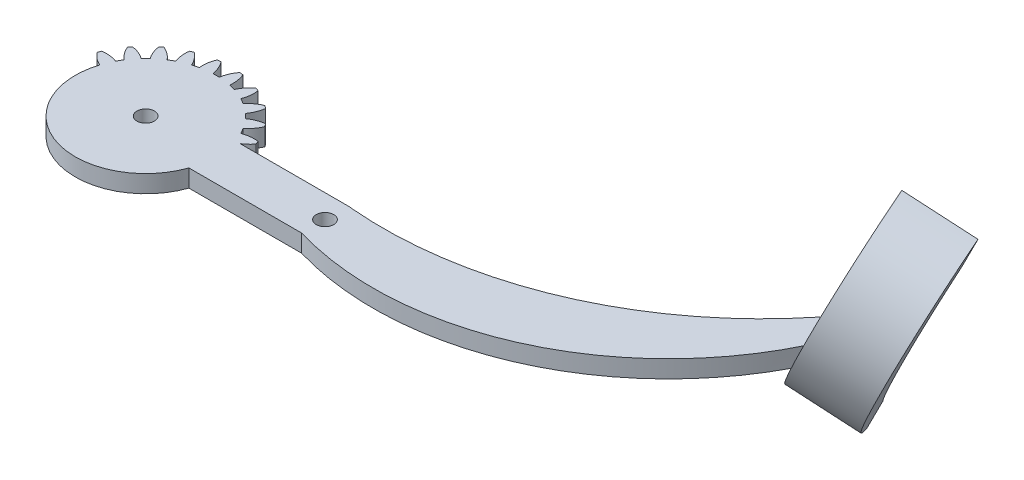
SolidWorks part; units mm, degrees
ref_plane "Front Plane" through (0, 0, 0) normal (0, 0, 1) x (1, 0, 0)
ref_plane "Top Plane" through (0, 0, 0) normal (0, 1, 0) x (1, 0, 0)
ref_plane "Right Plane" through (0, 0, 0) normal (1, 0, 0) x (0, 0, -1)
sketch "Sketch1" plane through (0, 0, 0) normal (0, 1, 0) x (1, 0, 0)
  line L0 (20.6437, 4) -> (2.0816, 4)
  line L1 (2.0816, -4) -> (20.6437, -4)
  arc A0 (2.0816, 4) -> (3.5217, 5.3071) centre (-0.7683, 8.5867) ccw
  arc A1 (3.5217, 5.3071) -> (3.2829, 5.8838) centre (-10.1063, 0) ccw
  arc A2 (3.2829, 5.8838) -> (0.6271, 5.5703) centre (2.5684, 0.5313) ccw
  arc A3 (0.6271, 5.5703) -> (0.0844, 6.5103) centre (-10.1063, 0) ccw
  arc A4 (0.0844, 6.5103) -> (1.6838, 8.6535) centre (-3.3089, 10.711) ccw
  arc A5 (1.6838, 8.6535) -> (1.3038, 9.1487) centre (-10.1063, 0) ccw
  arc A6 (1.3038, 9.1487) -> (-1.1803, 8.1585) centre (1.999, 3.7936) ccw
  arc A7 (-1.1803, 8.1585) -> (-1.9479, 8.926) centre (-10.1063, 0) ccw
  arc A8 (-1.9479, 8.926) -> (-0.9576, 11.4102) centre (-6.3127, 12.1053) ccw
  arc A9 (-0.9576, 11.4102) -> (-1.4528, 11.7901) centre (-10.1063, 0) ccw
  arc A10 (-1.4528, 11.7901) -> (-3.596, 10.1907) centre (0.6046, 6.7975) ccw
  arc A11 (-3.596, 10.1907) -> (-4.5361, 10.7334) centre (-10.1063, 0) ccw
  arc A12 (-4.5361, 10.7334) -> (-4.2225, 13.3892) centre (-9.5751, 12.6747) ccw
  arc A13 (-4.2225, 13.3892) -> (-4.7992, 13.6281) centre (-10.1063, 0) ccw
  arc A14 (-4.7992, 13.6281) -> (-6.4554, 11.5285) centre (-1.5196, 9.3381) ccw
  arc A15 (-6.4554, 11.5285) -> (-7.5039, 11.8094) centre (-10.1063, 0) ccw
  arc A16 (-7.5039, 11.8094) -> (-7.8884, 14.4558) centre (-12.8736, 12.3803) ccw
  arc A17 (-7.8884, 14.4558) -> (-8.5072, 14.5373) centre (-10.1063, 0) ccw
  arc A18 (-8.5072, 14.5373) -> (-9.5636, 12.0806) centre (-4.2291, 11.2423) ccw
  arc A19 (-9.5636, 12.0806) -> (-10.6491, 12.0806) centre (-10.1063, 0) ccw
  arc A20 (-10.6491, 12.0806) -> (-11.7054, 14.5373) centre (-15.9836, 11.2423) ccw
  arc A21 (-11.7054, 14.5373) -> (-12.3243, 14.4558) centre (-10.1063, 0) ccw
  arc A22 (-12.3243, 14.4558) -> (-12.7088, 11.8094) centre (-7.3391, 12.3803) ccw
  arc A23 (-12.7088, 11.8094) -> (-13.7573, 11.5285) centre (-10.1063, 0) ccw
  arc A24 (-13.7573, 11.5285) -> (-15.4135, 13.6281) centre (-18.6931, 9.3381) ccw
  arc A25 (-15.4135, 13.6281) -> (-15.9901, 13.3892) centre (-10.1063, 0) ccw
  arc A26 (-15.9901, 13.3892) -> (-15.6766, 10.7334) centre (-10.6376, 12.6747) ccw
  arc A27 (-15.6766, 10.7334) -> (-16.6166, 10.1907) centre (-10.1063, 0) ccw
  arc A28 (-16.6166, 10.1907) -> (-18.7599, 11.7901) centre (-20.8173, 6.7975) ccw
  arc A29 (-18.7599, 11.7901) -> (-19.255, 11.4102) centre (-10.1063, 0) ccw
  arc A30 (-19.255, 11.4102) -> (-18.2648, 8.926) centre (-13.9, 12.1053) ccw
  arc A31 (-18.2648, 8.926) -> (-19.0324, 8.1585) centre (-10.1063, 0) ccw
  arc A32 (-19.0324, 8.1585) -> (-21.5165, 9.1487) centre (-22.2117, 3.7936) ccw
  arc A33 (-21.5165, 9.1487) -> (-21.8965, 8.6535) centre (-10.1063, 0) ccw
  arc A34 (-21.8965, 8.6535) -> (-20.2971, 6.5103) centre (-16.9038, 10.711) ccw
  arc A35 (-20.2971, 6.5103) -> (-20.8398, 5.5703) centre (-10.1063, 0) ccw
  arc A36 (-20.8398, 5.5703) -> (-23.4956, 5.8838) centre (-22.7811, 0.5313) ccw
  arc A37 (-23.4956, 5.8838) -> (-23.7344, 5.3071) centre (-10.1063, 0) ccw
  arc A38 (-23.7344, 5.3071) -> (-21.6348, 3.6509) centre (-19.4444, 8.5867) ccw
  arc A39 (-21.6348, 3.6509) -> (-21.9157, 2.6025) centre (-10.1063, 0) ccw
  arc A40 (-21.9157, 2.6025) -> (-24.5622, 2.2179) centre (-22.4867, -2.7673) ccw
  arc A41 (-24.5622, 2.2179) -> (-24.6437, 1.5991) centre (-10.1063, 0) ccw
  arc A42 (-24.6437, 1.5991) -> (-22.1869, 0.5427) centre (-21.3486, 5.8773) ccw
  arc A43 (-22.1869, 0.5427) -> (-22.1869, -0.5427) centre (-10.1063, 0) ccw
  arc A44 (-22.1869, -0.5427) -> (-24.6437, -1.5991) centre (-21.3486, -5.8773) ccw
  arc A45 (-24.6437, -1.5991) -> (-24.5622, -2.2179) centre (-10.1063, 0) ccw
  arc A46 (-24.5622, -2.2179) -> (-21.9157, -2.6025) centre (-22.4867, 2.7673) ccw
  arc A47 (-21.9157, -2.6025) -> (-21.6348, -3.6509) centre (-10.1063, 0) ccw
  arc A48 (-21.6348, -3.6509) -> (-23.7344, -5.3071) centre (-19.4444, -8.5867) ccw
  arc A49 (-23.7344, -5.3071) -> (-23.4956, -5.8838) centre (-10.1063, 0) ccw
  arc A50 (-23.4956, -5.8838) -> (-20.8398, -5.5703) centre (-22.7811, -0.5313) ccw
  arc A51 (-20.8398, -5.5703) -> (-20.2971, -6.5103) centre (-10.1063, 0) ccw
  arc A52 (-20.2971, -6.5103) -> (-21.8965, -8.6535) centre (-16.9038, -10.711) ccw
  arc A53 (-21.8965, -8.6535) -> (-21.5165, -9.1487) centre (-10.1063, 0) ccw
  arc A54 (-21.5165, -9.1487) -> (-19.0324, -8.1585) centre (-22.2117, -3.7936) ccw
  arc A55 (-19.0324, -8.1585) -> (-18.2648, -8.926) centre (-10.1063, 0) ccw
  arc A56 (-18.2648, -8.926) -> (-19.255, -11.4102) centre (-13.9, -12.1053) ccw
  arc A57 (-19.255, -11.4102) -> (-18.7599, -11.7901) centre (-10.1063, 0) ccw
  arc A58 (-18.7599, -11.7901) -> (-16.6166, -10.1907) centre (-20.8173, -6.7975) ccw
  arc A59 (-16.6166, -10.1907) -> (-15.6766, -10.7334) centre (-10.1063, 0) ccw
  arc A60 (-15.6766, -10.7334) -> (-15.9901, -13.3892) centre (-10.6376, -12.6747) ccw
  arc A61 (-15.9901, -13.3892) -> (-15.4135, -13.6281) centre (-10.1063, 0) ccw
  arc A62 (-15.4135, -13.6281) -> (-13.7573, -11.5285) centre (-18.6931, -9.3381) ccw
  arc A63 (-13.7573, -11.5285) -> (-12.7088, -11.8094) centre (-10.1063, 0) ccw
  arc A64 (-12.7088, -11.8094) -> (-12.3243, -14.4558) centre (-7.3391, -12.3803) ccw
  arc A65 (-12.3243, -14.4558) -> (-11.7054, -14.5373) centre (-10.1063, 0) ccw
  arc A66 (-11.7054, -14.5373) -> (-10.6491, -12.0806) centre (-15.9836, -11.2423) ccw
  arc A67 (-10.6491, -12.0806) -> (-9.5636, -12.0806) centre (-10.1063, 0) ccw
  arc A68 (-9.5636, -12.0806) -> (-8.5072, -14.5373) centre (-4.2291, -11.2423) ccw
  arc A69 (-8.5072, -14.5373) -> (-7.8884, -14.4558) centre (-10.1063, 0) ccw
  arc A70 (-7.8884, -14.4558) -> (-7.5039, -11.8094) centre (-12.8736, -12.3803) ccw
  arc A71 (-7.5039, -11.8094) -> (-6.4554, -11.5285) centre (-10.1063, 0) ccw
  arc A72 (-6.4554, -11.5285) -> (-4.7992, -13.6281) centre (-1.5196, -9.3381) ccw
  arc A73 (-4.7992, -13.6281) -> (-4.2225, -13.3892) centre (-10.1063, 0) ccw
  arc A74 (-4.2225, -13.3892) -> (-4.5361, -10.7334) centre (-9.5751, -12.6747) ccw
  arc A75 (-4.5361, -10.7334) -> (-3.596, -10.1907) centre (-10.1063, 0) ccw
  arc A76 (-3.596, -10.1907) -> (-1.4528, -11.7901) centre (0.6046, -6.7975) ccw
  arc A77 (-1.4528, -11.7901) -> (-0.9576, -11.4102) centre (-10.1063, 0) ccw
  arc A78 (-0.9576, -11.4102) -> (-1.9479, -8.926) centre (-6.3127, -12.1053) ccw
  arc A79 (-1.9479, -8.926) -> (-1.1803, -8.1585) centre (-10.1063, 0) ccw
  arc A80 (-1.1803, -8.1585) -> (1.3038, -9.1487) centre (1.999, -3.7936) ccw
  arc A81 (1.3038, -9.1487) -> (1.6838, -8.6535) centre (-10.1063, 0) ccw
  arc A82 (1.6838, -8.6535) -> (0.0844, -6.5103) centre (-3.3089, -10.711) ccw
  arc A83 (0.0844, -6.5103) -> (0.6271, -5.5703) centre (-10.1063, 0) ccw
  arc A84 (0.6271, -5.5703) -> (3.2829, -5.8838) centre (2.5684, -0.5313) ccw
  arc A85 (3.2829, -5.8838) -> (3.5217, -5.3071) centre (-10.1063, 0) ccw
  arc A86 (3.5217, -5.3071) -> (2.0816, -4) centre (-0.7683, -8.5867) ccw
  arc A87 (20.6437, -4) -> (20.6437, 4) centre (20.6437, 0) ccw
  circle A88 centre (-10.1063, 0) radius 1.5
  circle A89 centre (20.6437, 0) radius 1.5
  dimension "D1" = 3
  dimension "D2" = 3
extrude "Boss-Extrude1" add sketch "Sketch1" along normal blind 3
sketch "Sketch2" plane through (0, 3, 0) normal (0, 1, 0) x (1, 0, 0)
  line L0 (2.0816, -4) -> (1.3057, -4)
  line L2 (20.6437, 4) -> (2.0816, 4)
  line L3 (2.0816, -4) -> (20.6437, -4)
  line L4 (20.6437, 4) -> (2.0816, 4)
  line L5 (2.0816, -4) -> (20.6437, -4)
  circle A0 centre (-10.1063, 0) radius 12.0927
  arc A88 (20.6437, -4) -> (20.6437, 4) centre (20.6437, 0) ccw
  arc A89 (2.0816, 4) -> (3.5217, 5.3071) centre (-0.7683, 8.5867) ccw
  arc A90 (3.5217, 5.3071) -> (3.2829, 5.8838) centre (-10.1063, 0) ccw
  arc A91 (3.2829, 5.8838) -> (0.6271, 5.5703) centre (2.5684, 0.5313) ccw
  arc A92 (0.6271, 5.5703) -> (0.0844, 6.5103) centre (-10.1063, 0) ccw
  arc A93 (0.0844, 6.5103) -> (1.6838, 8.6535) centre (-3.3089, 10.711) ccw
  arc A94 (1.6838, 8.6535) -> (1.3038, 9.1487) centre (-10.1063, 0) ccw
  arc A95 (1.3038, 9.1487) -> (-1.1803, 8.1585) centre (1.999, 3.7936) ccw
  arc A96 (-1.1803, 8.1585) -> (-1.9479, 8.926) centre (-10.1063, 0) ccw
  arc A97 (-1.9479, 8.926) -> (-0.9576, 11.4102) centre (-6.3127, 12.1053) ccw
  arc A98 (-0.9576, 11.4102) -> (-1.4528, 11.7901) centre (-10.1063, 0) ccw
  arc A99 (-1.4528, 11.7901) -> (-3.596, 10.1907) centre (0.6046, 6.7975) ccw
  arc A100 (-3.596, 10.1907) -> (-4.5361, 10.7334) centre (-10.1063, 0) ccw
  arc A101 (-4.5361, 10.7334) -> (-4.2225, 13.3892) centre (-9.5751, 12.6747) ccw
  arc A102 (-4.2225, 13.3892) -> (-4.7992, 13.6281) centre (-10.1063, 0) ccw
  arc A103 (-4.7992, 13.6281) -> (-6.4554, 11.5285) centre (-1.5196, 9.3381) ccw
  arc A104 (-6.4554, 11.5285) -> (-7.5039, 11.8094) centre (-10.1063, 0) ccw
  arc A105 (-7.5039, 11.8094) -> (-7.8884, 14.4558) centre (-12.8736, 12.3803) ccw
  arc A106 (-7.8884, 14.4558) -> (-8.5072, 14.5373) centre (-10.1063, 0) ccw
  arc A107 (-8.5072, 14.5373) -> (-9.5636, 12.0806) centre (-4.2291, 11.2423) ccw
  arc A108 (-9.5636, 12.0806) -> (-10.6491, 12.0806) centre (-10.1063, 0) ccw
  arc A109 (-10.6491, 12.0806) -> (-11.7054, 14.5373) centre (-15.9836, 11.2423) ccw
  arc A110 (-11.7054, 14.5373) -> (-12.3243, 14.4558) centre (-10.1063, 0) ccw
  arc A111 (-12.3243, 14.4558) -> (-12.7088, 11.8094) centre (-7.3391, 12.3803) ccw
  arc A112 (-12.7088, 11.8094) -> (-13.7573, 11.5285) centre (-10.1063, 0) ccw
  arc A113 (-13.7573, 11.5285) -> (-15.4135, 13.6281) centre (-18.6931, 9.3381) ccw
  arc A114 (-15.4135, 13.6281) -> (-15.9901, 13.3892) centre (-10.1063, 0) ccw
  arc A115 (-15.9901, 13.3892) -> (-15.6766, 10.7334) centre (-10.6376, 12.6747) ccw
  arc A116 (-15.6766, 10.7334) -> (-16.6166, 10.1907) centre (-10.1063, 0) ccw
  arc A117 (-16.6166, 10.1907) -> (-18.7599, 11.7901) centre (-20.8173, 6.7975) ccw
  arc A118 (-18.7599, 11.7901) -> (-19.255, 11.4102) centre (-10.1063, 0) ccw
  arc A119 (-19.255, 11.4102) -> (-18.2648, 8.926) centre (-13.9, 12.1053) ccw
  arc A120 (-18.2648, 8.926) -> (-19.0324, 8.1585) centre (-10.1063, 0) ccw
  arc A121 (-19.0324, 8.1585) -> (-21.5165, 9.1487) centre (-22.2117, 3.7936) ccw
  arc A122 (-21.5165, 9.1487) -> (-21.8965, 8.6535) centre (-10.1063, 0) ccw
  arc A123 (-21.8965, 8.6535) -> (-20.2971, 6.5103) centre (-16.9038, 10.711) ccw
  arc A124 (-20.2971, 6.5103) -> (-20.8398, 5.5703) centre (-10.1063, 0) ccw
  arc A125 (-20.8398, 5.5703) -> (-23.4956, 5.8838) centre (-22.7811, 0.5313) ccw
  arc A126 (-23.4956, 5.8838) -> (-23.7344, 5.3071) centre (-10.1063, 0) ccw
  arc A127 (-23.7344, 5.3071) -> (-21.6348, 3.6509) centre (-19.4444, 8.5867) ccw
  arc A128 (-21.6348, 3.6509) -> (-21.9157, 2.6025) centre (-10.1063, 0) ccw
  arc A129 (-21.9157, 2.6025) -> (-24.5622, 2.2179) centre (-22.4867, -2.7673) ccw
  arc A130 (-24.5622, 2.2179) -> (-24.6437, 1.5991) centre (-10.1063, 0) ccw
  arc A131 (-24.6437, 1.5991) -> (-22.1869, 0.5427) centre (-21.3486, 5.8773) ccw
  arc A132 (-22.1869, 0.5427) -> (-22.1869, -0.5427) centre (-10.1063, 0) ccw
  arc A133 (-22.1869, -0.5427) -> (-24.6437, -1.5991) centre (-21.3486, -5.8773) ccw
  arc A134 (-24.6437, -1.5991) -> (-24.5622, -2.2179) centre (-10.1063, 0) ccw
  arc A135 (-24.5622, -2.2179) -> (-21.9157, -2.6025) centre (-22.4867, 2.7673) ccw
  arc A136 (-21.9157, -2.6025) -> (-21.6348, -3.6509) centre (-10.1063, 0) ccw
  arc A137 (-21.6348, -3.6509) -> (-23.7344, -5.3071) centre (-19.4444, -8.5867) ccw
  arc A138 (-23.7344, -5.3071) -> (-23.4956, -5.8838) centre (-10.1063, 0) ccw
  arc A139 (-23.4956, -5.8838) -> (-20.8398, -5.5703) centre (-22.7811, -0.5313) ccw
  arc A140 (-20.8398, -5.5703) -> (-20.2971, -6.5103) centre (-10.1063, 0) ccw
  arc A141 (-20.2971, -6.5103) -> (-21.8965, -8.6535) centre (-16.9038, -10.711) ccw
  arc A142 (-21.8965, -8.6535) -> (-21.5165, -9.1487) centre (-10.1063, 0) ccw
  arc A143 (-21.5165, -9.1487) -> (-19.0324, -8.1585) centre (-22.2117, -3.7936) ccw
  arc A144 (-19.0324, -8.1585) -> (-18.2648, -8.926) centre (-10.1063, 0) ccw
  arc A145 (-18.2648, -8.926) -> (-19.255, -11.4102) centre (-13.9, -12.1053) ccw
  arc A146 (-19.255, -11.4102) -> (-18.7599, -11.7901) centre (-10.1063, 0) ccw
  arc A147 (-18.7599, -11.7901) -> (-16.6166, -10.1907) centre (-20.8173, -6.7975) ccw
  arc A148 (-16.6166, -10.1907) -> (-15.6766, -10.7334) centre (-10.1063, 0) ccw
  arc A149 (-15.6766, -10.7334) -> (-15.9901, -13.3892) centre (-10.6376, -12.6747) ccw
  arc A150 (-15.9901, -13.3892) -> (-15.4135, -13.6281) centre (-10.1063, 0) ccw
  arc A151 (-15.4135, -13.6281) -> (-13.7573, -11.5285) centre (-18.6931, -9.3381) ccw
  arc A152 (-13.7573, -11.5285) -> (-12.7088, -11.8094) centre (-10.1063, 0) ccw
  arc A153 (-12.7088, -11.8094) -> (-12.3243, -14.4558) centre (-7.3391, -12.3803) ccw
  arc A154 (-12.3243, -14.4558) -> (-11.7054, -14.5373) centre (-10.1063, 0) ccw
  arc A155 (-11.7054, -14.5373) -> (-10.6491, -12.0806) centre (-15.9836, -11.2423) ccw
  arc A156 (-10.6491, -12.0806) -> (-9.5636, -12.0806) centre (-10.1063, 0) ccw
  arc A157 (-9.5636, -12.0806) -> (-8.5072, -14.5373) centre (-4.2291, -11.2423) ccw
  arc A158 (-8.5072, -14.5373) -> (-7.8884, -14.4558) centre (-10.1063, 0) ccw
  arc A159 (-7.8884, -14.4558) -> (-7.5039, -11.8094) centre (-12.8736, -12.3803) ccw
  arc A160 (-7.5039, -11.8094) -> (-6.4554, -11.5285) centre (-10.1063, 0) ccw
  arc A161 (-6.4554, -11.5285) -> (-4.7992, -13.6281) centre (-1.5196, -9.3381) ccw
  arc A162 (-4.7992, -13.6281) -> (-4.2225, -13.3892) centre (-10.1063, 0) ccw
  arc A163 (-4.2225, -13.3892) -> (-4.5361, -10.7334) centre (-9.5751, -12.6747) ccw
  arc A164 (-4.5361, -10.7334) -> (-3.596, -10.1907) centre (-10.1063, 0) ccw
  arc A165 (-3.596, -10.1907) -> (-1.4528, -11.7901) centre (0.6046, -6.7975) ccw
  arc A166 (-1.4528, -11.7901) -> (-0.9576, -11.4102) centre (-10.1063, 0) ccw
  arc A167 (-0.9576, -11.4102) -> (-1.9479, -8.926) centre (-6.3127, -12.1053) ccw
  arc A168 (-1.9479, -8.926) -> (-1.1803, -8.1585) centre (-10.1063, 0) ccw
  arc A169 (-1.1803, -8.1585) -> (1.3038, -9.1487) centre (1.999, -3.7936) ccw
  arc A170 (1.3038, -9.1487) -> (1.6838, -8.6535) centre (-10.1063, 0) ccw
  arc A171 (1.6838, -8.6535) -> (0.0844, -6.5103) centre (-3.3089, -10.711) ccw
  arc A172 (0.0844, -6.5103) -> (0.6271, -5.5703) centre (-10.1063, 0) ccw
  arc A173 (0.6271, -5.5703) -> (3.2829, -5.8838) centre (2.5684, -0.5313) ccw
  arc A174 (3.2829, -5.8838) -> (3.5217, -5.3071) centre (-10.1063, 0) ccw
  arc A175 (3.5217, -5.3071) -> (2.0816, -4) centre (-0.7683, -8.5867) ccw
  arc A176 (20.6437, -4) -> (20.6437, 4) centre (20.6437, 0) ccw
  arc A177 (2.0816, 4) -> (3.5217, 5.3071) centre (-0.7683, 8.5867) ccw
  arc A178 (3.5217, 5.3071) -> (3.2829, 5.8838) centre (-10.1063, 0) ccw
  arc A179 (3.2829, 5.8838) -> (0.6271, 5.5703) centre (2.5684, 0.5313) ccw
  arc A180 (0.6271, 5.5703) -> (0.0844, 6.5103) centre (-10.1063, 0) ccw
  arc A181 (0.0844, 6.5103) -> (1.6838, 8.6535) centre (-3.3089, 10.711) ccw
  arc A182 (1.6838, 8.6535) -> (1.3038, 9.1487) centre (-10.1063, 0) ccw
  arc A183 (1.3038, 9.1487) -> (-1.1803, 8.1585) centre (1.999, 3.7936) ccw
  arc A184 (-1.1803, 8.1585) -> (-1.9479, 8.926) centre (-10.1063, 0) ccw
  arc A185 (-1.9479, 8.926) -> (-0.9576, 11.4102) centre (-6.3127, 12.1053) ccw
  arc A186 (-0.9576, 11.4102) -> (-1.4528, 11.7901) centre (-10.1063, 0) ccw
  arc A187 (-1.4528, 11.7901) -> (-3.596, 10.1907) centre (0.6046, 6.7975) ccw
  arc A188 (-3.596, 10.1907) -> (-4.5361, 10.7334) centre (-10.1063, 0) ccw
  arc A189 (-4.5361, 10.7334) -> (-4.2225, 13.3892) centre (-9.5751, 12.6747) ccw
  arc A190 (-4.2225, 13.3892) -> (-4.7992, 13.6281) centre (-10.1063, 0) ccw
  arc A191 (-4.7992, 13.6281) -> (-6.4554, 11.5285) centre (-1.5196, 9.3381) ccw
  arc A192 (-6.4554, 11.5285) -> (-7.5039, 11.8094) centre (-10.1063, 0) ccw
  arc A193 (-7.5039, 11.8094) -> (-7.8884, 14.4558) centre (-12.8736, 12.3803) ccw
  arc A194 (-7.8884, 14.4558) -> (-8.5072, 14.5373) centre (-10.1063, 0) ccw
  arc A195 (-8.5072, 14.5373) -> (-9.5636, 12.0806) centre (-4.2291, 11.2423) ccw
  arc A196 (-9.5636, 12.0806) -> (-10.6491, 12.0806) centre (-10.1063, 0) ccw
  arc A197 (-10.6491, 12.0806) -> (-11.7054, 14.5373) centre (-15.9836, 11.2423) ccw
  arc A198 (-11.7054, 14.5373) -> (-12.3243, 14.4558) centre (-10.1063, 0) ccw
  arc A199 (-12.3243, 14.4558) -> (-12.7088, 11.8094) centre (-7.3391, 12.3803) ccw
  arc A200 (-12.7088, 11.8094) -> (-13.7573, 11.5285) centre (-10.1063, 0) ccw
  arc A201 (-13.7573, 11.5285) -> (-15.4135, 13.6281) centre (-18.6931, 9.3381) ccw
  arc A202 (-15.4135, 13.6281) -> (-15.9901, 13.3892) centre (-10.1063, 0) ccw
  arc A203 (-15.9901, 13.3892) -> (-15.6766, 10.7334) centre (-10.6376, 12.6747) ccw
  arc A204 (-15.6766, 10.7334) -> (-16.6166, 10.1907) centre (-10.1063, 0) ccw
  arc A205 (-16.6166, 10.1907) -> (-18.7599, 11.7901) centre (-20.8173, 6.7975) ccw
  arc A206 (-18.7599, 11.7901) -> (-19.255, 11.4102) centre (-10.1063, 0) ccw
  arc A207 (-19.255, 11.4102) -> (-18.2648, 8.926) centre (-13.9, 12.1053) ccw
  arc A208 (-18.2648, 8.926) -> (-19.0324, 8.1585) centre (-10.1063, 0) ccw
  arc A209 (-19.0324, 8.1585) -> (-21.5165, 9.1487) centre (-22.2117, 3.7936) ccw
  arc A210 (-21.5165, 9.1487) -> (-21.8965, 8.6535) centre (-10.1063, 0) ccw
  arc A211 (-21.8965, 8.6535) -> (-20.2971, 6.5103) centre (-16.9038, 10.711) ccw
  arc A212 (-20.2971, 6.5103) -> (-20.8398, 5.5703) centre (-10.1063, 0) ccw
  arc A213 (-20.8398, 5.5703) -> (-23.4956, 5.8838) centre (-22.7811, 0.5313) ccw
  arc A214 (-23.4956, 5.8838) -> (-23.7344, 5.3071) centre (-10.1063, 0) ccw
  arc A215 (-23.7344, 5.3071) -> (-21.6348, 3.6509) centre (-19.4444, 8.5867) ccw
  arc A216 (-21.6348, 3.6509) -> (-21.9157, 2.6025) centre (-10.1063, 0) ccw
  arc A217 (-21.9157, 2.6025) -> (-24.5622, 2.2179) centre (-22.4867, -2.7673) ccw
  arc A218 (-24.5622, 2.2179) -> (-24.6437, 1.5991) centre (-10.1063, 0) ccw
  arc A219 (-24.6437, 1.5991) -> (-22.1869, 0.5427) centre (-21.3486, 5.8773) ccw
  arc A220 (-22.1869, 0.5427) -> (-22.1869, -0.5427) centre (-10.1063, 0) ccw
  arc A221 (-22.1869, -0.5427) -> (-24.6437, -1.5991) centre (-21.3486, -5.8773) ccw
  arc A222 (-24.6437, -1.5991) -> (-24.5622, -2.2179) centre (-10.1063, 0) ccw
  arc A223 (-24.5622, -2.2179) -> (-21.9157, -2.6025) centre (-22.4867, 2.7673) ccw
  arc A224 (-21.9157, -2.6025) -> (-21.6348, -3.6509) centre (-10.1063, 0) ccw
  arc A225 (-21.6348, -3.6509) -> (-23.7344, -5.3071) centre (-19.4444, -8.5867) ccw
  arc A226 (-23.7344, -5.3071) -> (-23.4956, -5.8838) centre (-10.1063, 0) ccw
  arc A227 (-23.4956, -5.8838) -> (-20.8398, -5.5703) centre (-22.7811, -0.5313) ccw
  arc A228 (-20.8398, -5.5703) -> (-20.2971, -6.5103) centre (-10.1063, 0) ccw
  arc A229 (-20.2971, -6.5103) -> (-21.8965, -8.6535) centre (-16.9038, -10.711) ccw
  arc A230 (-21.8965, -8.6535) -> (-21.5165, -9.1487) centre (-10.1063, 0) ccw
  arc A231 (-21.5165, -9.1487) -> (-19.0324, -8.1585) centre (-22.2117, -3.7936) ccw
  arc A232 (-19.0324, -8.1585) -> (-18.2648, -8.926) centre (-10.1063, 0) ccw
  arc A233 (-18.2648, -8.926) -> (-19.255, -11.4102) centre (-13.9, -12.1053) ccw
  arc A234 (-19.255, -11.4102) -> (-18.7599, -11.7901) centre (-10.1063, 0) ccw
  arc A235 (-18.7599, -11.7901) -> (-16.6166, -10.1907) centre (-20.8173, -6.7975) ccw
  arc A236 (-16.6166, -10.1907) -> (-15.6766, -10.7334) centre (-10.1063, 0) ccw
  arc A237 (-15.6766, -10.7334) -> (-15.9901, -13.3892) centre (-10.6376, -12.6747) ccw
  arc A238 (-15.9901, -13.3892) -> (-15.4135, -13.6281) centre (-10.1063, 0) ccw
  arc A239 (-15.4135, -13.6281) -> (-13.7573, -11.5285) centre (-18.6931, -9.3381) ccw
  arc A240 (-13.7573, -11.5285) -> (-12.7088, -11.8094) centre (-10.1063, 0) ccw
  arc A241 (-12.7088, -11.8094) -> (-12.3243, -14.4558) centre (-7.3391, -12.3803) ccw
  arc A242 (-12.3243, -14.4558) -> (-11.7054, -14.5373) centre (-10.1063, 0) ccw
  arc A243 (-11.7054, -14.5373) -> (-10.6491, -12.0806) centre (-15.9836, -11.2423) ccw
  arc A244 (-10.6491, -12.0806) -> (-9.5636, -12.0806) centre (-10.1063, 0) ccw
  arc A245 (-9.5636, -12.0806) -> (-8.5072, -14.5373) centre (-4.2291, -11.2423) ccw
  arc A246 (-8.5072, -14.5373) -> (-7.8884, -14.4558) centre (-10.1063, 0) ccw
  arc A247 (-7.8884, -14.4558) -> (-7.5039, -11.8094) centre (-12.8736, -12.3803) ccw
  arc A248 (-7.5039, -11.8094) -> (-6.4554, -11.5285) centre (-10.1063, 0) ccw
  arc A249 (-6.4554, -11.5285) -> (-4.7992, -13.6281) centre (-1.5196, -9.3381) ccw
  arc A250 (-4.7992, -13.6281) -> (-4.2225, -13.3892) centre (-10.1063, 0) ccw
  arc A251 (-4.2225, -13.3892) -> (-4.5361, -10.7334) centre (-9.5751, -12.6747) ccw
  arc A252 (-4.5361, -10.7334) -> (-3.596, -10.1907) centre (-10.1063, 0) ccw
  arc A253 (-3.596, -10.1907) -> (-1.4528, -11.7901) centre (0.6046, -6.7975) ccw
  arc A254 (-1.4528, -11.7901) -> (-0.9576, -11.4102) centre (-10.1063, 0) ccw
  arc A255 (-0.9576, -11.4102) -> (-1.9479, -8.926) centre (-6.3127, -12.1053) ccw
  arc A256 (-1.9479, -8.926) -> (-1.1803, -8.1585) centre (-10.1063, 0) ccw
  arc A257 (-1.1803, -8.1585) -> (1.3038, -9.1487) centre (1.999, -3.7936) ccw
  arc A258 (1.3038, -9.1487) -> (1.6838, -8.6535) centre (-10.1063, 0) ccw
  arc A259 (1.6838, -8.6535) -> (0.0844, -6.5103) centre (-3.3089, -10.711) ccw
  arc A260 (0.0844, -6.5103) -> (0.6271, -5.5703) centre (-10.1063, 0) ccw
  arc A261 (0.6271, -5.5703) -> (3.2829, -5.8838) centre (2.5684, -0.5313) ccw
  arc A262 (3.2829, -5.8838) -> (3.5217, -5.3071) centre (-10.1063, 0) ccw
  arc A263 (3.5217, -5.3071) -> (2.0816, -4) centre (-0.7683, -8.5867) ccw
  dimension "D1" = 0
extrude "Cut-Extrude1" cut sketch "Sketch2" against normal blind 10 contours A222 A223 A0 A221 | A226 A227 A0 A225 | A230 A231 A0 A229 | A234 A235 A0 A233 | A238 A239 A0 A237 | A242 A243 A0 A241 | A246 A247 A0 A245 | A250 A251 A0 A249 | A254 A255 A0 A253 | A258 A259 A0 A257 | A262 A263 L0 A0 A261 | A218 A219 A0 A217 region at (2.066, 3, 5.0775) region at (0.3325, 3, 8.01) region at (-2.0963, 3, 10.4389) region at (-5.071, 3, 12.1563) region at (-8.3889, 3, 13.0454) region at (-11.8238, 3, 13.0454) region at (-15.1417, 3, 12.1563) region at (-18.1164, 3, 10.4389) region at (-20.5452, 3, 8.01) region at (-22.2627, 3, 5.0353) region at (-23.1517, 3, 1.7175) region at (-23.1517, 3, -1.7175)
sketch "Sketch3" plane through (0, 0, 0) normal (0, -1, 0) x (-1, 0, 0)
  line L0 (-1.3057, -4) -> (-20.6437, -4) construction
  line L1 (-84.5348, 34.1348) -> (-79.2561, 30.1844)
  line L2 (-32.7165, 63.4333) -> (-51.8853, 17.2544) construction
  arc A0 (-20.6437, 4) -> (-79.2561, 30.1844) centre (-26.9139, 68.657) cw
  arc A1 (-20.6437, -4) -> (-84.5348, 34.1348) centre (-34.9378, 44.6407) cw
  arc A2 (-20.6437, 4) -> (-20.6437, -4) centre (-20.6437, 0) ccw construction
  arc A3 (-20.6437, -4) -> (-20.6437, 4) centre (-20.6437, 0) cw
  arc M44 (-20.6437, 4) -> (-20.6437, -4) centre (-20.6437, 0) ccw
  dimension "D1" = 30.2366
  dimension "D2" = 36.6264
extrude "Boss-Extrude2" add sketch "Sketch3" against normal blind 3 contours A1 A0 L1 M44 region at (53.9889, 0, -6.9962)
sketch "Sketch6" plane through (83.6973, -41.2284, -34.5205) normal (0.8413, -0.4144, -0.347) x (-0.3113, 0.1533, -0.9379)
  line L0 (5.8393, 55.8353) -> (6.7086, 60.7592)
  line L3 (0.0895, 23.2691) -> (8.7829, 72.5076) construction
  line L5 (0.6233, 26.2922) -> (1.4926, 31.2161)
  line L7 (708.7551, -51.006) -> (-638.4091, 186.8444) construction
  arc A3 (5.8393, 55.8353) -> (1.4926, 31.2161) centre (16.4205, 41.2738) ccw
  arc A5 (0.6233, 26.2922) -> (6.7086, 60.7592) centre (10.9526, 42.2392) cw
  dimension "D5" = 18
  dimension "D6" = 19
  dimension "D1" = 12
  dimension "D2" = 17
  dimension "D3" = 42
  dimension "D4" = 47
extrude "Boss-Extrude3" add sketch "Sketch6" along normal blind 11 from offset 25 offset against normal yes
sketch "Sketch7" plane through (71.9187, -35.4264, -29.6625) normal (0.8413, -0.4144, -0.347) x (-0.3113, 0.1533, -0.9379)
  line L0 (5.8393, 55.8353) -> (1.4926, 31.2161)
  line L1 (5.8393, 55.8353) -> (10.1201, 55.0795)
  line L2 (10.1201, 55.0795) -> (5.4216, 30.1527)
  line L3 (5.4216, 30.1527) -> (1.4926, 31.2161)
extrude "Cut-Extrude2" cut sketch "Sketch7" against normal blind 18
